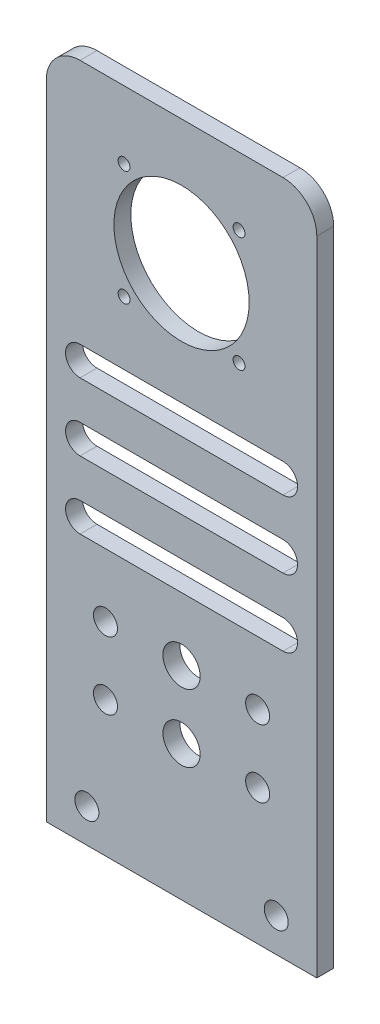
SolidWorks part; units mm, degrees
ref_plane "前视基准面" through (0, 0, 0) normal (0, 0, 1) x (1, 0, 0)
ref_plane "上视基准面" through (0, 0, 0) normal (0, 1, 0) x (1, 0, 0)
ref_plane "右视基准面" through (0, 0, 0) normal (1, 0, 0) x (0, 0, -1)
other "Configuration Table"
sketch "草图1" plane through (0, 0, 0) normal (0, 0, 1) x (1, 0, 0)
  line L0 (0, 0) -> (0, 10)
  line L1 (0, 0) -> (80, 0)
  line L2 (0, 0) -> (0, 200)
  line L3 (0, 200) -> (80, 200)
  line L4 (80, 0) -> (80, 200)
  line L5 (0, 10) -> (80, 10)
  line L6 (40, 10) -> (68, 10)
  line L7 (40, -990) -> (40, 49010) construction
  line L8 (40, 10) -> (40, 40)
  line L9 (40, 40) -> (62.5, 40)
  line L10 (40, 200) -> (40, 180)
  line L11 (40, 180) -> (57, 180)
  line L12 (40, 180) -> (40, 146)
  line L13 (40, 146) -> (57, 146)
  line L14 (40, 163) -> (40, 123)
  line L15 (10, 123) -> (70, 123)
  line L16 (70, 123) -> (10, 123) construction
  line L17 (70, 118.7) -> (10, 118.7)
  line L18 (70, 127.3) -> (10, 127.3)
  circle A0 centre (68, 10) radius 3.55
  circle A1 centre (12, 10) radius 3.55
  circle A2 centre (62.5, 40) radius 3.55
  circle A3 centre (17.5, 40) radius 3.55
  circle A4 centre (40, 40) radius 5.5
  circle A5 centre (40, 40) radius 50
  circle A6 centre (57, 180) radius 1.75
  circle A7 centre (23, 180) radius 1.75
  circle A8 centre (57, 146) radius 1.75
  circle A9 centre (23, 146) radius 1.75
  circle A10 centre (40, 163) radius 20
  circle A11 centre (40, 163) radius 15
  arc A12 (70, 118.7) -> (70, 127.3) centre (70, 123) ccw
  arc A13 (10, 127.3) -> (10, 118.7) centre (10, 123) ccw
  point P38 (40, 123)
  dimension "D5" = 7.1
  dimension "D8" = 7.1
  dimension "D9" = 11
  dimension "D10" = 100
  dimension "D13" = 3.5
  dimension "D16" = 3.5
  dimension "D17" = 40
  dimension "D20" = 30
  dimension "D21" = 4.3
  dimension "D1" = 200
  dimension "D2" = 80
  dimension "D3" = 10
  dimension "D4" = 28
  dimension "D6" = 30
  dimension "D7" = 22.5
  dimension "D11" = 20
  dimension "D12" = 17
  dimension "D14" = 34
  dimension "D15" = 17
  dimension "D18" = 40
  dimension "D19" = 30
extrude "凸台-拉伸1" add sketch "草图1" along normal blind 5 contours A13 L18 A10 L3 L2 A5 L4 A6 A8 A12 L17 A7 A9 | L4 A5 L2 L5 A1 A4 A2 A0 A3 | L5 A5 L1 A0 A1 | A5 L1 L4 | A5 L0 L1 region at (3.1736, 3.1736, 0) region at (40, 47.6773, 0) region at (40, 5.0403, 0) region at (1.5264, 135, 0) region at (76.8264, 3.1736, 0)
fillet "圆角1" radius 10 1 edges at (0, 200, 2.5) type face fillet first side face at (40, 200, 2.5) second side face at (0, 100, 2.5)
fillet "圆角2" radius 10 1 edges at (80, 200, 2.5) type face fillet first side face at (45, 200, 2.5) second side face at (80, 100, 2.5)
sketch "草图2" plane through (0, 0, 5) normal (0, 0, 1) x (1, 0, 0)
  line L0 (40, -960) -> (40, 49040) construction
  line L1 (10, 123) -> (70, 123) construction
  line L2 (10, 127.3) -> (70, 127.3)
  line L3 (10, 118.7) -> (70, 118.7)
  line L4 (10, 103) -> (70, 103) construction
  line L5 (10, 107.3) -> (70, 107.3)
  line L6 (10, 98.7) -> (70, 98.7)
  line L7 (10, 83) -> (70, 83) construction
  line L8 (10, 87.3) -> (70, 87.3)
  line L9 (10, 78.7) -> (70, 78.7)
  circle A0 centre (17.5, 40) radius 3.55
  circle A1 centre (40, 40) radius 5.5
  circle A2 centre (62.5, 40) radius 3.55
  circle A3 centre (62.5, 60) radius 3.55
  circle A4 centre (40, 60) radius 5.5
  circle A5 centre (17.5, 60) radius 3.55
  arc A6 (10, 127.3) -> (10, 118.7) centre (10, 123) ccw
  arc A7 (70, 118.7) -> (70, 127.3) centre (70, 123) ccw
  arc A8 (10, 107.3) -> (10, 98.7) centre (10, 103) ccw
  arc A9 (70, 98.7) -> (70, 107.3) centre (70, 103) ccw
  arc A10 (10, 87.3) -> (10, 78.7) centre (10, 83) ccw
  arc A11 (70, 78.7) -> (70, 87.3) centre (70, 83) ccw
  point P21 (40, 123)
  point P30 (40, 103)
  point P37 (40, 83)
  dimension "D2" = 4.3
  dimension "D1" = 2
  dimension "D3" = 3
extrude "切除-拉伸2" cut sketch "草图2" against normal through all
